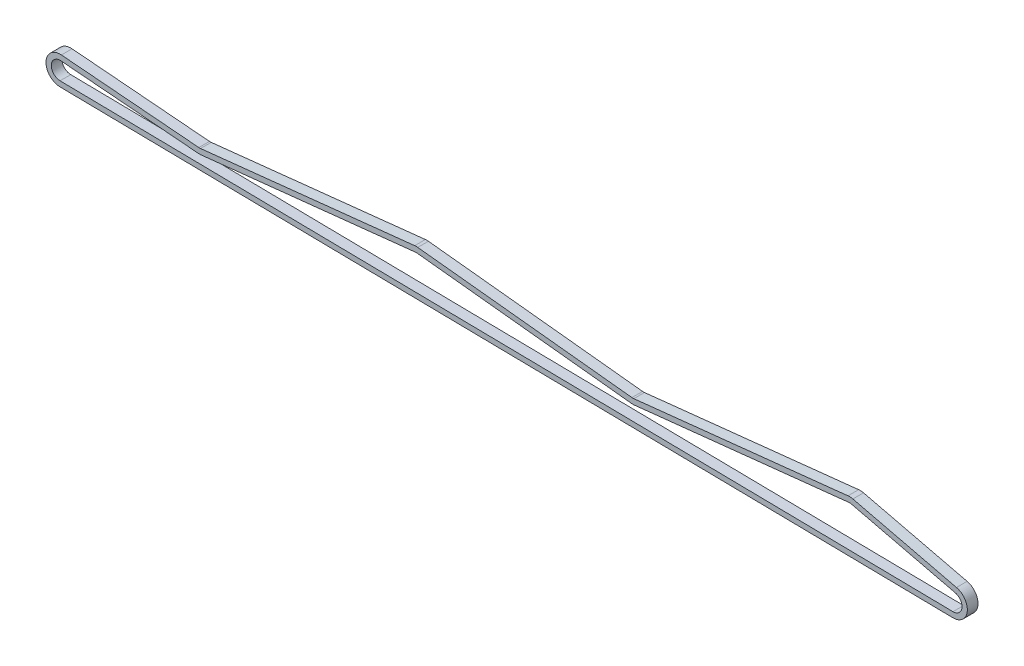
SolidWorks part; units mm, degrees
ref_plane "Front Plane" through (0, 0, 0) normal (0, 0, 1) x (1, 0, 0)
ref_plane "Top Plane" through (0, 0, 0) normal (0, 1, 0) x (1, 0, 0)
ref_plane "Right Plane" through (0, 0, 0) normal (1, 0, 0) x (0, 0, -1)
sketch "Sketch1" plane through (0, 0, 0) normal (0, 0, 1) x (1, 0, 0)
  line L15 (307.2526, -12.9991) -> (-195.5912, -5.4991)
  line L16 (-194.8072, 10.4723) -> (-117.3873, 4.0173)
  line L17 (-116.4391, 4.0285) -> (4.1756, 16.9545)
  line L18 (5.8806, 16.9545) -> (126.4953, 4.0285)
  line L19 (127.5609, 4.0285) -> (248.1756, 16.9545)
  line L20 (250.8948, 16.7792) -> (309.2386, 2.7792)
  line L21 (-195.0565, 7.4827) -> (-117.6366, 1.0277)
  line L22 (-116.1194, 1.0455) -> (4.4953, 13.9715)
  line L23 (5.5609, 13.9715) -> (126.1756, 1.0455)
  line L24 (127.8806, 1.0455) -> (248.4953, 13.9715)
  line L25 (250.1948, 13.862) -> (308.5386, -0.138)
  line L26 (307.2973, -9.9994) -> (-195.5465, -2.4994)
  circle A0 centre (307.3719, -5) radius 5 construction
  circle A2 centre (249.0281, 9) radius 5 construction
  circle A3 centre (127.0281, 9) radius 5 construction
  circle A4 centre (5.0281, 9) radius 5 construction
  circle A5 centre (-116.9719, 9) radius 5 construction
  circle A6 centre (-195.4719, 2.5) radius 5 construction
  circle A7 centre (307.3719, -5) radius 5 construction
  circle A9 centre (249.0281, 9) radius 5 construction
  circle A10 centre (127.0281, 9) radius 5 construction
  circle A11 centre (5.0281, 9) radius 5 construction
  circle A12 centre (-116.9719, 9) radius 5 construction
  circle A13 centre (-195.4719, 2.5) radius 5 construction
  arc A25 (-194.8072, 10.4723) -> (-195.5912, -5.4991) centre (-195.4719, 2.5) ccw
  arc A26 (-117.3873, 4.0173) -> (-116.4391, 4.0285) centre (-116.9719, 9) ccw
  arc A27 (4.1756, 16.9545) -> (5.8806, 16.9545) centre (5.0281, 9) cw
  arc A28 (126.4953, 4.0285) -> (127.5609, 4.0285) centre (127.0281, 9) ccw
  arc A29 (248.1756, 16.9545) -> (250.8948, 16.7792) centre (249.0281, 9) cw
  arc A30 (309.2386, 2.7792) -> (307.2526, -12.9991) centre (307.3719, -5) cw
  arc A31 (-117.6366, 1.0277) -> (-116.1194, 1.0455) centre (-116.9719, 9) ccw
  arc A32 (4.4953, 13.9715) -> (5.5609, 13.9715) centre (5.0281, 9) cw
  arc A33 (126.1756, 1.0455) -> (127.8806, 1.0455) centre (127.0281, 9) ccw
  arc A34 (248.4953, 13.9715) -> (250.1948, 13.862) centre (249.0281, 9) cw
  arc A35 (308.5386, -0.138) -> (307.2973, -9.9994) centre (307.3719, -5) cw
  arc A36 (-195.0565, 7.4827) -> (-195.5465, -2.4994) centre (-195.4719, 2.5) ccw
  point P0 (28.0936, 2.0889)
  point P8 (-113.9677, 5.7093)
  point P10 (159.9806, -9.6681)
  point P37 (-115.5275, 1.0277)
  point P54 (-195.291, 10.6976)
  point P55 (0, 0)
  point P56 (-43.777, 15.9147)
  point P57 (0, 0)
  point P58 (0, 0)
  point P59 (0, 0)
  dimension "D1" = 3
extrude "Boss-Extrude1" add sketch "Sketch1" along normal mid plane 6
